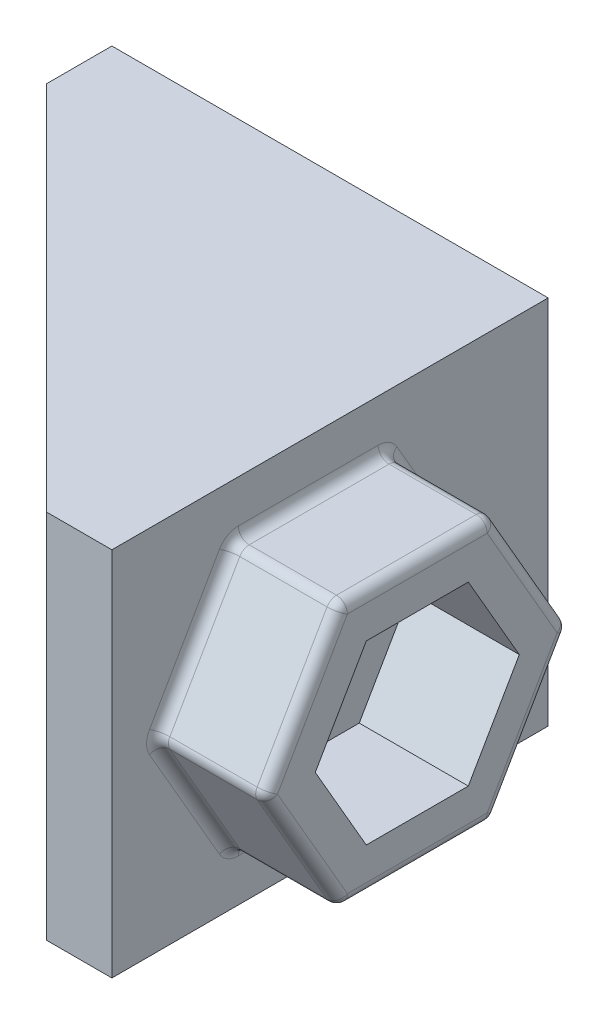
SolidWorks part; units mm, degrees
ref_plane "Alzado" through (0, 0, 0) normal (0, 0, 1) x (1, 0, 0)
ref_plane "Planta" through (0, 0, 0) normal (0, 1, 0) x (1, 0, 0)
ref_plane "Vista lateral" through (0, 0, 0) normal (1, 0, 0) x (0, 0, -1)
sketch "Croquis2" plane through (0, 0, 0) normal (0, 0, 1) x (1, 0, 0)
  line L1 (-10, 8.5) -> (10, 8.5)
  line L2 (-10, 8.5) -> (-10, -8.5)
  line L3 (-10, -8.5) -> (10, -8.5)
  line L4 (10, 8.5) -> (10, -8.5)
  line L5 (-10, 8.5) -> (10, -8.5) construction
  line L6 (-10, -8.5) -> (10, 8.5) construction
  point P0 (0, 0)
  dimension "D1" = 17
  dimension "D2" = 20
extrude "Saliente-Extruir1" add sketch "Croquis2" along normal mid plane 3
ref_plane "Plano1" through (7, 0, 0) normal (1, 0, 0) x (0, 0, -1)
sketch "Croquis3" plane through (7, 0, 0) normal (1, 0, 0) x (0, 0, -1)
  line L1 (-18.5, 8.5) -> (1.5, 8.5)
  line L2 (-18.5, 8.5) -> (-18.5, -8.5)
  line L3 (-18.5, -8.5) -> (1.5, -8.5)
  line L4 (1.5, 8.5) -> (1.5, -8.5)
  line L5 (-18.5, 8.5) -> (1.5, -8.5) construction
  line L6 (-18.5, -8.5) -> (1.5, 8.5) construction
  point P0 (-8.5, 0)
  dimension "D1" = 20
extrude "Saliente-Extruir2" add sketch "Croquis3" along normal blind 3
sketch "Croquis4" plane through (0, 0, 1.5) normal (0, 0, 1) x (1, 0, 0)
  point P0 (0, 0)
hole_wizard "Ranura de margen para M65" positions "Croquis7" profile "Croquis8" size "M6" standard "DIN" slot yes end condition through all
sketch "Croquis7" plane through (0, 0, 1.5) normal (0, 0, 1) x (1, 0, 0)
  line L2 (-5.5, 0) -> (3.5, 0) construction
  line L3 (10, -8.5) -> (10, 8.5) construction
  point P0 (-1, 0)
  dimension "D1" = 9
  dimension "D2" = 11
sketch "Croquis8" plane through (-1, 0, 1.5) normal (1, 0, 0) x (0, -1, 0)
  line L0 (0, 0) -> (0, 3)
  line L1 (0, 3) -> (3, 3)
  line L2 (3, 3) -> (3, 0)
  line L5 (3, 0) -> (0, 0)
  line L11 (0, -6.35) -> (0, 107.95) construction
  dimension "Diámetro de taladro hasta el siguiente" = 6
  dimension "Profundidad de taladro hasta el siguiente" = 3
fillet "Redondeo1" radius 0.5 1 edges at (7, 0, 1.5)
sketch "Croquis9" plane through (0, -8.5, 0) normal (0, -1, 0) x (1, 0, 0)
  line L0 (7, 18.5) -> (-10, 1.5)
  line L1 (-10, 1.5) -> (-10, -1.5)
  line L2 (-10, -1.5) -> (10, -1.5)
  line L3 (10, -1.5) -> (10, 18.5)
  line L4 (10, 18.5) -> (7, 18.5)
extrude "Saliente-Extruir3" add sketch "Croquis9" against normal blind 3
mirror "Simetría2" about plane through (0, 0, 0) normal (0, 1, 0) of "Saliente-Extruir3"
hole_wizard "Taladro de margen para M51" positions "Croquis10" profile "Croquis11" hole size "M5" standard "DIN" end condition through all
sketch "Croquis10" plane through (7, 0, 0) normal (-1, 0, 0) x (0, 0, 1)
  line L1 (-1.5, -8.5) -> (-1.5, 8.5) construction
  point P0 (9.5, 0)
  dimension "D2" = 11
sketch "Croquis11" plane through (7, 0, 9.5) normal (0, 1, 0) x (0, 0, 1)
  line L0 (0, 0) -> (0, 3)
  line L1 (0, 3) -> (2.65, 3)
  line L2 (2.65, 3) -> (2.65, 0)
  line L5 (2.65, 0) -> (0, 0)
  line L11 (0, -6.35) -> (0, 107.95) construction
  dimension "Diámetro de taladro hasta el siguiente" = 5.3
  dimension "Profundidad de taladro hasta el siguiente" = 3
sketch "Croquis12" plane through (10, 0, 0) normal (1, 0, 0) x (0, 0, -1)
  line L1 (-7.1617, -4.05) -> (-4.8235, 0)
  line L2 (-6.007, -6.05) -> (-2.5141, 0)
  line L3 (-2.5141, 0) -> (-6.007, 6.05)
  line L4 (-6.007, 6.05) -> (-12.993, 6.05)
  line L5 (-12.993, 6.05) -> (-16.4859, 0)
  line L6 (-16.4859, 0) -> (-12.993, -6.05)
  line L7 (-12.993, -6.05) -> (-6.007, -6.05)
  line L8 (-4.8235, 0) -> (-7.1617, 4.05)
  line L9 (-7.1617, 4.05) -> (-11.8383, 4.05)
  line L10 (-11.8383, 4.05) -> (-14.1765, 0)
  line L11 (-14.1765, 0) -> (-11.8383, -4.05)
  line L12 (-11.8383, -4.05) -> (-7.1617, -4.05)
  circle A0 centre (-9.5, 0) radius 6.05 construction
  circle A1 centre (-9.5, 0) radius 4.05 construction
  dimension "D1" = 2
  dimension "D2" = 8.1
extrude "Saliente-Extruir4" add sketch "Croquis12" along normal blind 5
fillet "Redondeo2" radius 0.5 18 edges at (15, 3.025, 14.7395) (10, 3.025, 14.7395) (15, 6.05, 9.5) (12.5, 6.05, 12.993) (10, 6.05, 9.5) (15, 3.025, 4.2605) (12.5, 6.05, 6.007) (10, 3.025, 4.2605) (15, -3.025, 4.2605) (12.5, 0, 2.5141) (10, -3.025, 4.2605) (15, -6.05, 9.5) (12.5, -6.05, 6.007) (10, -6.05, 9.5) (12.5, 0, 16.4859) (15, -3.025, 14.7395) (12.5, -6.05, 12.993) (10, -3.025, 14.7395)
